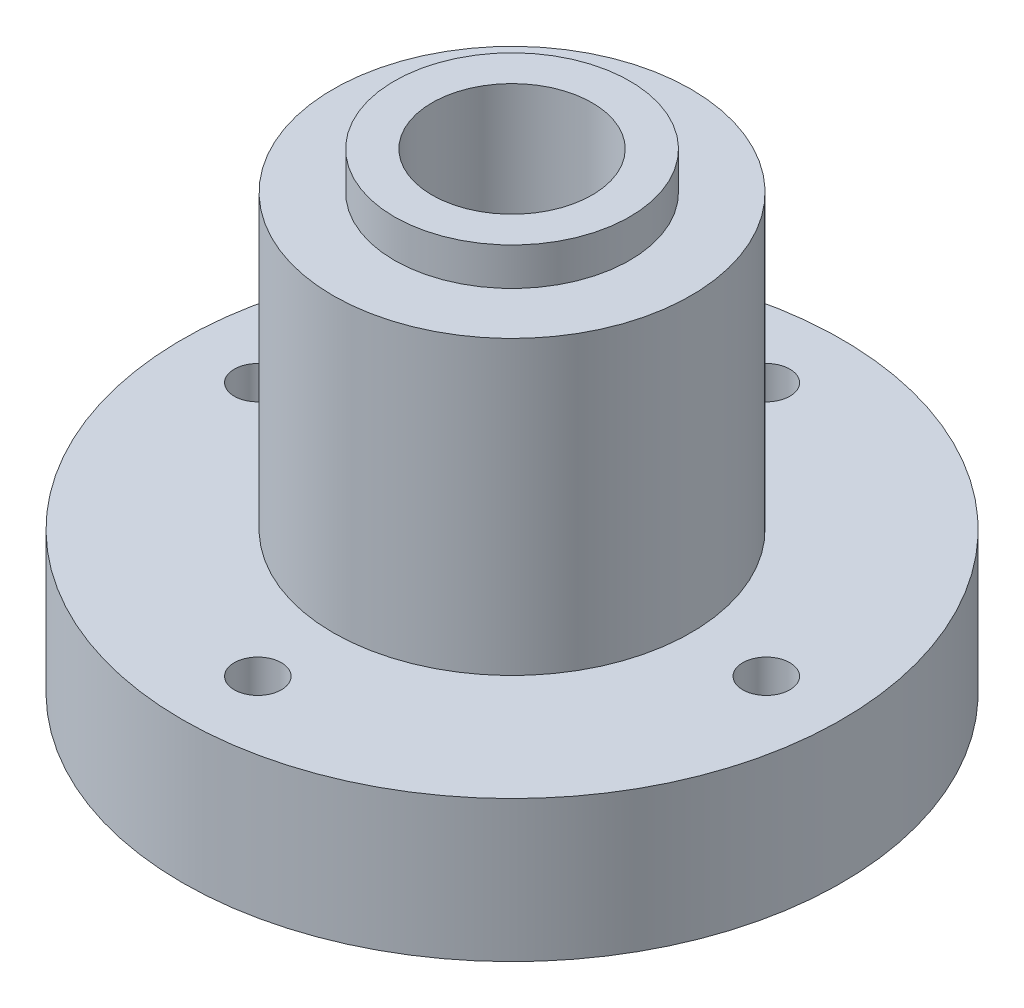
SolidWorks part; units mm, degrees
ref_plane "Front Plane" through (0, 0, 0) normal (0, 0, 1) x (1, 0, 0)
ref_plane "Top Plane" through (0, 0, 0) normal (0, 1, 0) x (1, 0, 0)
ref_plane "Right Plane" through (0, 0, 0) normal (1, 0, 0) x (0, 0, -1)
ref_axis "X" through (-88.99, 0, 0) along (1, 0, 0)
ref_axis "Y" through (0, 0, -88.99) along (0, 0, 1)
ref_axis "Z" through (0, 55, 0) along (0, -1, 0)
sketch "Sketch1" plane through (0, 0, 0) normal (0, 0, 1) x (1, 0, 0)
  line L0 (0, 0) -> (0, -29.6934) construction
  line L1 (-8.5, 0) -> (-35, 0)
  line L2 (-35, 0) -> (-35, 15)
  line L3 (-35, 15) -> (-19, 15)
  line L4 (-19, 15) -> (-19, 46)
  line L5 (-12.5, 50) -> (-8.5, 50)
  line L7 (-8.5, 50) -> (-8.5, 0)
  line L8 (-19, 46) -> (-12.5, 46)
  line L9 (-12.5, 46) -> (-12.5, 50)
  dimension "D1" = 15
  dimension "D2" = 35
  dimension "D3" = 38
  dimension "D4" = 17
  dimension "D5" = 25
  dimension "D6" = 70
  dimension "D7" = 4
revolve "Revolve1" add sketch "Sketch1" angle 360 about L0
hole_wizard "M6 Tapped Hole1" positions "Sketch2" profile "Sketch3" tap size "M6" standard "DIN" end condition through all
sketch "Sketch2" plane through (0, 15, 0) normal (0, 1, 0) x (1, 0, 0)
  line L0 (-27, 0) -> (0, 0) construction
  line L1 (0, 0) -> (27, 0) construction
  line L3 (0, -27) -> (0, 0) construction
  line L4 (0, 0) -> (0, 27) construction
  point P0 (-27, 0)
  point P2 (0, 27)
  point P4 (27, 0)
  point P6 (0, -27)
  dimension "D1" = 27
sketch "Sketch3" plane through (-27, 15, 0) normal (1, 0, 0) x (0, 0, 1)
  line L0 (0, 0) -> (0, 15)
  line L1 (0, 15) -> (2.5, 15)
  line L2 (2.5, 15) -> (2.5, 0)
  line L5 (2.5, 0) -> (0, 0)
  line L11 (0, -6.35) -> (0, 107.95) construction
  dimension "Thread Major Dia." = 5
  dimension "Thru Tap Drill Depth" = 15
sketch "Sketch4" plane through (0, 0, 0) normal (0, -1, 0) x (1, 0, 0)
  circle A0 centre (0, 0) radius 16
  dimension "D1" = 32
extrude "Cut-Extrude1" cut sketch "Sketch4" against normal blind 9
